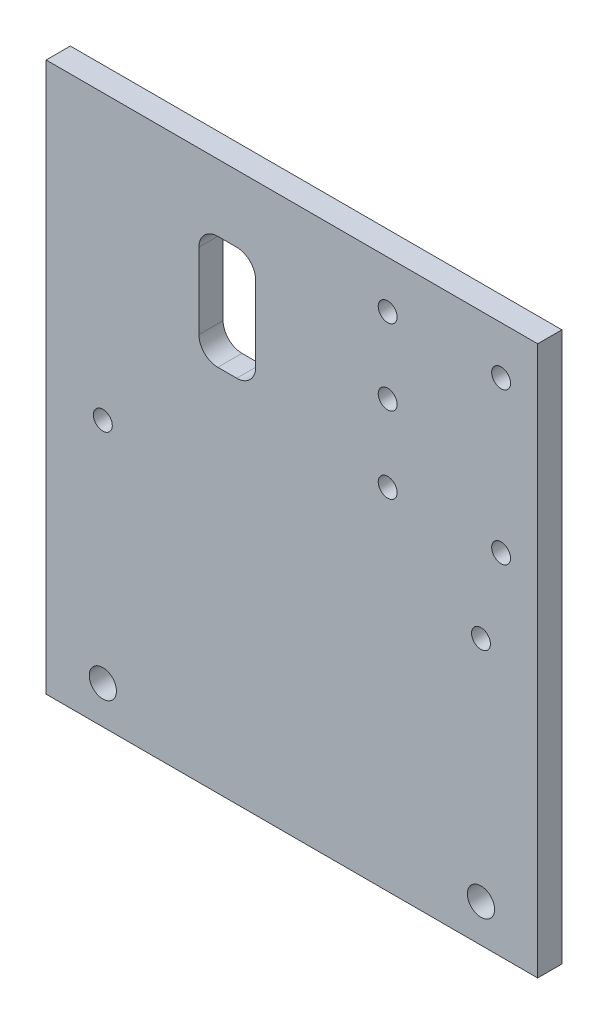
SolidWorks part; units mm, degrees
ref_plane "Front Plane" through (0, 0, 0) normal (0, 0, 1) x (1, 0, 0)
ref_plane "Top Plane" through (0, 0, 0) normal (0, 1, 0) x (1, 0, 0)
ref_plane "Right Plane" through (0, 0, 0) normal (1, 0, 0) x (0, 0, -1)
sketch "Sketch1" plane through (0, 0, 0) normal (0, 0, 1) x (1, 0, 0)
  line L0 (75.33, 84.625) -> (75.33, 80.485) construction
  line L5 (0, 0) -> (100, 0) construction
  line L6 (0, 0) -> (0, 60.26) construction
  line L7 (0, 60.26) -> (100, 60.26) construction
  line L8 (100, 0) -> (100, 60.26) construction
  line L9 (0, 0) -> (100, 60.26) construction
  line L10 (0, 60.26) -> (100, 0) construction
  line L11 (-15, -10) -> (115, -10)
  line L12 (-15, -10) -> (-15, 135.26)
  line L13 (-15, 135.26) -> (115, 135.26)
  line L14 (115, -10) -> (115, 135.26)
  line L15 (-15, -10) -> (115, 135.26) construction
  line L16 (-15, 135.26) -> (115, -10) construction
  line L17 (58.97, 84.625) -> (109.14, 84.625) construction
  line L18 (109.14, 80.485) -> (58.97, 80.485) construction
  line L19 (105.33, 124.705) -> (105.33, 120.565) construction
  line L20 (58.97, 124.705) -> (109.14, 124.705) construction
  line L21 (109.14, 120.565) -> (58.97, 120.565) construction
  line L22 (105.33, 84.625) -> (105.33, 80.485) construction
  line L23 (75.33, 122.7664) -> (75.33, 84.625) construction
  circle A0 centre (0, 0) radius 3.6
  circle A1 centre (0, 60.26) radius 2.5
  circle A2 centre (100, 60.26) radius 2.5
  circle A3 centre (100, 0) radius 3.6
  circle A4 centre (75.33, 82.555) radius 2.5
  circle A5 centre (105.33, 82.555) radius 2.5
  circle A6 centre (105.33, 122.635) radius 2.5
  circle A8 centre (75.33, 102.7664) radius 2.5
  circle A9 centre (75.33, 122.7664) radius 2.5
  point P6 (50, 30.13)
  point P16 (50, 62.63)
  dimension "D1" = 7.2
  dimension "D3" = 5
  dimension "D9" = 30
  dimension "D10" = 5
  dimension "D11" = 5
  dimension "D12" = 5
  dimension "D13" = 5
  dimension "D2" = 60.26
  dimension "D4" = 100
  dimension "D5" = 15
  dimension "D6" = 15
  dimension "D7" = 10
  dimension "D8" = 75
extrude "Boss-Extrude1" add sketch "Sketch1" along normal blind 6.4
sketch "Sketch2" plane through (0, 0, 0) normal (0, 0, -1) x (-1, 0, 0)
  line L0 (-115, 135.26) -> (15, 135.26) construction
  line L1 (-40.4075, 87.5704) -> (-25.4075, 87.5704)
  line L2 (-40.4075, 87.5704) -> (-40.4075, 117.5704)
  line L3 (-40.4075, 117.5704) -> (-25.4075, 117.5704)
  line L4 (-25.4075, 87.5704) -> (-25.4075, 117.5704)
  line L5 (-40.4075, 87.5704) -> (-25.4075, 117.5704) construction
  line L6 (-40.4075, 117.5704) -> (-25.4075, 87.5704) construction
  point P4 (-32.9075, 102.5704)
  dimension "D1" = 30
  dimension "D2" = 15
  dimension "D3" = 17.6896
extrude "Cut-Extrude1" cut sketch "Sketch2" against normal through all
fillet "Fillet1" radius 5 4 edges at (25.4075, 117.5704, 3.2) (40.4075, 117.5704, 3.2) (25.4075, 87.5704, 3.2) (40.4075, 87.5704, 3.2)
